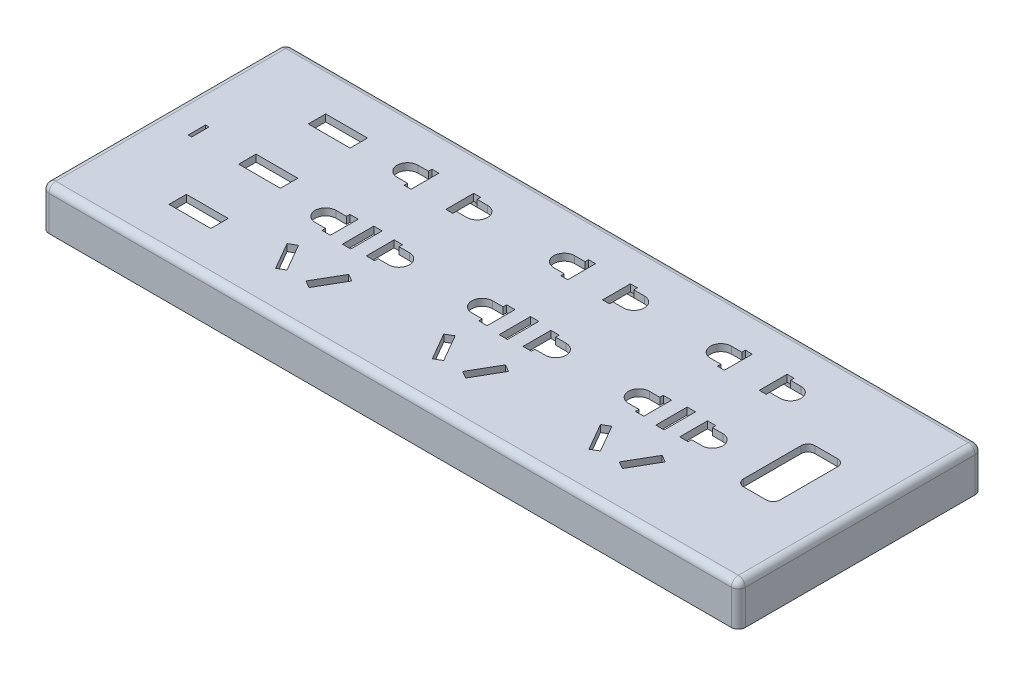
SolidWorks part; units mm, degrees
material "ABS"
ref_plane "前视基准面" through (0, 0, 0) normal (0, 0, 1) x (1, 0, 0)
ref_plane "上视基准面" through (0, 0, 0) normal (0, 1, 0) x (1, 0, 0)
ref_plane "右视基准面" through (0, 0, 0) normal (1, 0, 0) x (0, 0, -1)
ref_plane "BoxInnerTop" through (0, 0, 0) normal (0, 1, 0) x (1, 0, 0)
ref_plane "ConnectFace" through (0, -10, 0) normal (0, 1, 0) x (1, 0, 0)
sketch "SketchRec" plane through (0, 0, 0) normal (0, 1, 0) x (1, 0, 0)
  line L1 (-100, -35) -> (100, -35)
  line L2 (-100, -35) -> (-100, 35)
  line L3 (-100, 35) -> (100, 35)
  line L4 (100, -35) -> (100, 35)
  line L5 (-100, -35) -> (100, 35) construction
  line L6 (-100, 35) -> (100, -35) construction
  point P0 (0, 0)
  dimension "L" = 200
  dimension "KD" = 70
extrude "RectangleBox" add sketch "SketchRec" along normal blind 2 and the other way blind 10
fillet "RectangleR" radius 2 8 edges at (-100, -4, 35) (-100, -4, -35) (100, -4, -35) (100, -4, 35) (100, 2, 0) (0, 2, -35) (-100, 2, 0) (0, 2, 35)
shell "RectangleC" thickness 2 removed face at (0, -10, 0)
sketch "SketchCircle" [suppressed] plane through (0, 0, 0) normal (0, 1, 0) x (1, 0, 0)
  circle A0 centre (0, 0) radius 80
  dimension "D1" = 160
extrude "CircleBox" [suppressed] add sketch "SketchCircle" along normal blind 2 and the other way blind 10 contours A0
fillet "CircleR" [suppressed] radius 2
shell "CircleC" [suppressed] thickness 2
sketch "SButtonCut" plane through (0, -10, 0) normal (0, 1, 0) x (1, 0, 0)
  line L4 (83.25, 10.25) -> (76.75, 10.25)
  line L5 (85.25, -8.25) -> (85.25, 8.25)
  line L6 (76.75, -10.25) -> (83.25, -10.25)
  line L7 (74.75, 8.25) -> (74.75, -8.25)
  line L8 (83.25, 10.25) -> (76.75, 10.25)
  line L9 (85.25, -8.25) -> (85.25, 8.25)
  line L10 (76.75, -10.25) -> (83.25, -10.25)
  line L11 (74.75, 8.25) -> (74.75, -8.25)
  arc A4 (85.25, 8.25) -> (83.25, 10.25) centre (83.25, 8.25) ccw
  arc A5 (83.25, -10.25) -> (85.25, -8.25) centre (83.25, -8.25) ccw
  arc A6 (74.75, -8.25) -> (76.75, -10.25) centre (76.75, -8.25) ccw
  arc A7 (76.75, 10.25) -> (74.75, 8.25) centre (76.75, 8.25) ccw
  arc A8 (85.25, 8.25) -> (83.25, 10.25) centre (83.25, 8.25) ccw
  arc A9 (83.25, -10.25) -> (85.25, -8.25) centre (83.25, -8.25) ccw
  arc A10 (74.75, -8.25) -> (76.75, -10.25) centre (76.75, -8.25) ccw
  arc A11 (76.75, 10.25) -> (74.75, 8.25) centre (76.75, 8.25) ccw
  dimension "D1" = 0
extrude "FButtonCut" cut sketch "SButtonCut" along normal through all
sketch "SLEDCut" plane through (0, -10, 0) normal (0, 1, 0) x (1, 0, 0)
  line L4 (-90.5, -2.5) -> (-89.5, -2.5)
  line L5 (-89.5, -2.5) -> (-89.5, 2.5)
  line L6 (-89.5, 2.5) -> (-90.5, 2.5)
  line L7 (-90.5, 2.5) -> (-90.5, -2.5)
  line L8 (-90.5, -2.5) -> (-89.5, -2.5)
  line L9 (-89.5, -2.5) -> (-89.5, 2.5)
  line L10 (-89.5, 2.5) -> (-90.5, 2.5)
  line L11 (-90.5, 2.5) -> (-90.5, -2.5)
  dimension "D1" = 0
extrude "FLEDCut" cut sketch "SLEDCut" along normal through all
sketch "SSlotA" plane through (0, -10, 0) normal (0, 1, 0) x (1, 0, 0)
  line L4 (-38.8, 1.5) -> (-41.2, 1.5)
  line L5 (-38.8, -7.5) -> (-38.8, 1.5)
  line L6 (-41.2, -7.5) -> (-38.8, -7.5)
  line L7 (-45.15, -7) -> (-45.15, 1)
  line L8 (-47.55, -7) -> (-45.15, -7)
  line L9 (-47.55, -6) -> (-47.55, -7)
  line L10 (-50.55, -6) -> (-47.55, -6)
  line L11 (-47.55, 0) -> (-50.55, 0)
  line L12 (-47.55, 1) -> (-47.55, 0)
  line L13 (-45.15, 1) -> (-47.55, 1)
  line L14 (-45.15, -7) -> (-45.15, 1)
  line L15 (-47.55, -7) -> (-45.15, -7)
  line L16 (-47.55, -6) -> (-47.55, -7)
  line L17 (-50.55, -6) -> (-47.55, -6)
  line L18 (-47.55, 0) -> (-50.55, 0)
  line L19 (-47.55, 1) -> (-47.55, 0)
  line L20 (-45.15, 1) -> (-47.55, 1)
  line L21 (-41.2, 1.5) -> (-41.2, -7.5)
  line L22 (-38.8, 1.5) -> (-41.2, 1.5)
  line L23 (-38.8, -7.5) -> (-38.8, 1.5)
  line L24 (-41.2, -7.5) -> (-38.8, -7.5)
  line L25 (-41.2, 1.5) -> (-41.2, -7.5)
  line L26 (-37.2831, -21.8942) -> (-35.2047, -23.0942)
  line L27 (-35.2047, -23.0942) -> (-30.7047, -15.3)
  line L28 (-30.7047, -15.3) -> (-32.7831, -14.1)
  line L29 (-32.45, 0) -> (-32.45, 1)
  line L30 (-29.45, 0) -> (-32.45, 0)
  line L31 (-32.45, -6) -> (-29.45, -6)
  line L32 (-32.45, -7) -> (-32.45, -6)
  line L33 (-34.85, -7) -> (-32.45, -7)
  line L34 (-34.85, 1) -> (-34.85, -7)
  line L35 (-32.45, 1) -> (-34.85, 1)
  line L36 (-32.45, 0) -> (-32.45, 1)
  line L37 (-29.45, 0) -> (-32.45, 0)
  line L38 (-32.45, -6) -> (-29.45, -6)
  line L39 (-32.45, -7) -> (-32.45, -6)
  line L40 (-34.85, -7) -> (-32.45, -7)
  line L41 (-34.85, 1) -> (-34.85, -7)
  line L42 (-32.45, 1) -> (-34.85, 1)
  line L43 (-32.7831, -14.1) -> (-37.2831, -21.8942)
  line L44 (-37.2831, -21.8942) -> (-35.2047, -23.0942)
  line L45 (-35.2047, -23.0942) -> (-30.7047, -15.3)
  line L46 (-30.7047, -15.3) -> (-32.7831, -14.1)
  line L47 (-32.7831, -14.1) -> (-37.2831, -21.8942)
  line L48 (-49.2953, -15.3) -> (-44.7953, -23.0942)
  line L49 (-47.2169, -14.1) -> (-49.2953, -15.3)
  line L50 (-42.7169, -21.8942) -> (-47.2169, -14.1)
  line L51 (-44.7953, -23.0942) -> (-42.7169, -21.8942)
  line L52 (-49.2953, -15.3) -> (-44.7953, -23.0942)
  line L53 (-47.2169, -14.1) -> (-49.2953, -15.3)
  line L54 (-42.7169, -21.8942) -> (-47.2169, -14.1)
  line L55 (-44.7953, -23.0942) -> (-42.7169, -21.8942)
  arc A1 (-50.55, 0) -> (-50.55, -6) centre (-50.55, -3) ccw
  arc A2 (-50.55, 0) -> (-50.55, -6) centre (-50.55, -3) ccw
  arc A3 (-29.45, -6) -> (-29.45, 0) centre (-29.45, -3) ccw
  arc A4 (-29.45, -6) -> (-29.45, 0) centre (-29.45, -3) ccw
  dimension "D1" = 0
  dimension "D2" = 0
  dimension "D3" = 0
  dimension "D4" = 0
  dimension "D5" = 0
extrude "FSlotACut" cut sketch "SSlotA" along normal through all
sketch "SSlotA2" plane through (0, -10, 0) normal (0, 1, 0) x (1, 0, 0)
  line L4 (6.2, 1.5) -> (3.8, 1.5)
  line L5 (6.2, -7.5) -> (6.2, 1.5)
  line L6 (3.8, -7.5) -> (6.2, -7.5)
  line L7 (-0.15, -7) -> (-0.15, 1)
  line L8 (-2.55, -7) -> (-0.15, -7)
  line L9 (-2.55, -6) -> (-2.55, -7)
  line L10 (-5.55, -6) -> (-2.55, -6)
  line L11 (-2.55, 0) -> (-5.55, 0)
  line L12 (-2.55, 1) -> (-2.55, 0)
  line L13 (-0.15, 1) -> (-2.55, 1)
  line L14 (-0.15, -7) -> (-0.15, 1)
  line L15 (-2.55, -7) -> (-0.15, -7)
  line L16 (-2.55, -6) -> (-2.55, -7)
  line L17 (-5.55, -6) -> (-2.55, -6)
  line L18 (-2.55, 0) -> (-5.55, 0)
  line L19 (-2.55, 1) -> (-2.55, 0)
  line L20 (-0.15, 1) -> (-2.55, 1)
  line L21 (3.8, 1.5) -> (3.8, -7.5)
  line L22 (6.2, 1.5) -> (3.8, 1.5)
  line L23 (6.2, -7.5) -> (6.2, 1.5)
  line L24 (3.8, -7.5) -> (6.2, -7.5)
  line L25 (3.8, 1.5) -> (3.8, -7.5)
  line L26 (7.7169, -21.8942) -> (9.7953, -23.0942)
  line L27 (9.7953, -23.0942) -> (14.2953, -15.3)
  line L28 (14.2953, -15.3) -> (12.2169, -14.1)
  line L29 (12.55, 0) -> (12.55, 1)
  line L30 (15.55, 0) -> (12.55, 0)
  line L31 (12.55, -6) -> (15.55, -6)
  line L32 (12.55, -7) -> (12.55, -6)
  line L33 (10.15, -7) -> (12.55, -7)
  line L34 (10.15, 1) -> (10.15, -7)
  line L35 (12.55, 1) -> (10.15, 1)
  line L36 (12.55, 0) -> (12.55, 1)
  line L37 (15.55, 0) -> (12.55, 0)
  line L38 (12.55, -6) -> (15.55, -6)
  line L39 (12.55, -7) -> (12.55, -6)
  line L40 (10.15, -7) -> (12.55, -7)
  line L41 (10.15, 1) -> (10.15, -7)
  line L42 (12.55, 1) -> (10.15, 1)
  line L43 (12.2169, -14.1) -> (7.7169, -21.8942)
  line L44 (7.7169, -21.8942) -> (9.7953, -23.0942)
  line L45 (9.7953, -23.0942) -> (14.2953, -15.3)
  line L46 (14.2953, -15.3) -> (12.2169, -14.1)
  line L47 (12.2169, -14.1) -> (7.7169, -21.8942)
  line L48 (-4.2953, -15.3) -> (0.2047, -23.0942)
  line L49 (-2.2169, -14.1) -> (-4.2953, -15.3)
  line L50 (2.2831, -21.8942) -> (-2.2169, -14.1)
  line L51 (0.2047, -23.0942) -> (2.2831, -21.8942)
  line L52 (-4.2953, -15.3) -> (0.2047, -23.0942)
  line L53 (-2.2169, -14.1) -> (-4.2953, -15.3)
  line L54 (2.2831, -21.8942) -> (-2.2169, -14.1)
  line L55 (0.2047, -23.0942) -> (2.2831, -21.8942)
  arc A1 (-5.55, 0) -> (-5.55, -6) centre (-5.55, -3) ccw
  arc A2 (-5.55, 0) -> (-5.55, -6) centre (-5.55, -3) ccw
  arc A3 (15.55, -6) -> (15.55, 0) centre (15.55, -3) ccw
  arc A4 (15.55, -6) -> (15.55, 0) centre (15.55, -3) ccw
  dimension "D1" = 0
  dimension "D2" = 0
  dimension "D3" = 0
  dimension "D4" = 0
  dimension "D5" = 0
extrude "FSlotA2Cut" cut sketch "SSlotA2" along normal through all
sketch "SSlotA3" plane through (0, -10, 0) normal (0, 1, 0) x (1, 0, 0)
  line L4 (51.2, 1.5) -> (48.8, 1.5)
  line L5 (51.2, -7.5) -> (51.2, 1.5)
  line L6 (48.8, -7.5) -> (51.2, -7.5)
  line L7 (44.85, -7) -> (44.85, 1)
  line L8 (42.45, -7) -> (44.85, -7)
  line L9 (42.45, -6) -> (42.45, -7)
  line L10 (39.45, -6) -> (42.45, -6)
  line L11 (42.45, 0) -> (39.45, 0)
  line L12 (42.45, 1) -> (42.45, 0)
  line L13 (44.85, 1) -> (42.45, 1)
  line L14 (44.85, -7) -> (44.85, 1)
  line L15 (42.45, -7) -> (44.85, -7)
  line L16 (42.45, -6) -> (42.45, -7)
  line L17 (39.45, -6) -> (42.45, -6)
  line L18 (42.45, 0) -> (39.45, 0)
  line L19 (42.45, 1) -> (42.45, 0)
  line L20 (44.85, 1) -> (42.45, 1)
  line L21 (48.8, 1.5) -> (48.8, -7.5)
  line L22 (51.2, 1.5) -> (48.8, 1.5)
  line L23 (51.2, -7.5) -> (51.2, 1.5)
  line L24 (48.8, -7.5) -> (51.2, -7.5)
  line L25 (48.8, 1.5) -> (48.8, -7.5)
  line L26 (52.7169, -21.8942) -> (54.7953, -23.0942)
  line L27 (54.7953, -23.0942) -> (59.2953, -15.3)
  line L28 (59.2953, -15.3) -> (57.2169, -14.1)
  line L29 (57.55, 0) -> (57.55, 1)
  line L30 (60.55, 0) -> (57.55, 0)
  line L31 (57.55, -6) -> (60.55, -6)
  line L32 (57.55, -7) -> (57.55, -6)
  line L33 (55.15, -7) -> (57.55, -7)
  line L34 (55.15, 1) -> (55.15, -7)
  line L35 (57.55, 1) -> (55.15, 1)
  line L36 (57.55, 0) -> (57.55, 1)
  line L37 (60.55, 0) -> (57.55, 0)
  line L38 (57.55, -6) -> (60.55, -6)
  line L39 (57.55, -7) -> (57.55, -6)
  line L40 (55.15, -7) -> (57.55, -7)
  line L41 (55.15, 1) -> (55.15, -7)
  line L42 (57.55, 1) -> (55.15, 1)
  line L43 (57.2169, -14.1) -> (52.7169, -21.8942)
  line L44 (52.7169, -21.8942) -> (54.7953, -23.0942)
  line L45 (54.7953, -23.0942) -> (59.2953, -15.3)
  line L46 (59.2953, -15.3) -> (57.2169, -14.1)
  line L47 (57.2169, -14.1) -> (52.7169, -21.8942)
  line L48 (40.7047, -15.3) -> (45.2047, -23.0942)
  line L49 (42.7831, -14.1) -> (40.7047, -15.3)
  line L50 (47.2831, -21.8942) -> (42.7831, -14.1)
  line L51 (45.2047, -23.0942) -> (47.2831, -21.8942)
  line L52 (40.7047, -15.3) -> (45.2047, -23.0942)
  line L53 (42.7831, -14.1) -> (40.7047, -15.3)
  line L54 (47.2831, -21.8942) -> (42.7831, -14.1)
  line L55 (45.2047, -23.0942) -> (47.2831, -21.8942)
  arc A1 (39.45, 0) -> (39.45, -6) centre (39.45, -3) ccw
  arc A2 (39.45, 0) -> (39.45, -6) centre (39.45, -3) ccw
  arc A3 (60.55, -6) -> (60.55, 0) centre (60.55, -3) ccw
  arc A4 (60.55, -6) -> (60.55, 0) centre (60.55, -3) ccw
  dimension "D1" = 0
  dimension "D2" = 0
  dimension "D3" = 0
  dimension "D4" = 0
  dimension "D5" = 0
extrude "FSlotA3Cut" cut sketch "SSlotA3" along normal through all
sketch "SSlotB" plane through (0, -10, 0) normal (0, 1, 0) x (1, 0, 0)
  line L7 (-45, 16) -> (-45, 24)
  line L8 (-47, 16) -> (-45, 16)
  line L9 (-47, 17) -> (-47, 16)
  line L10 (-50, 17) -> (-47, 17)
  line L11 (-47, 23) -> (-50, 23)
  line L12 (-47, 24) -> (-47, 23)
  line L13 (-45, 24) -> (-47, 24)
  line L14 (-45, 16) -> (-45, 24)
  line L15 (-47, 16) -> (-45, 16)
  line L16 (-47, 17) -> (-47, 16)
  line L17 (-50, 17) -> (-47, 17)
  line L18 (-47, 23) -> (-50, 23)
  line L19 (-47, 24) -> (-47, 23)
  line L20 (-45, 24) -> (-47, 24)
  line L21 (-33, 17) -> (-30, 17)
  line L22 (-30, 23) -> (-33, 23)
  line L23 (-33, 23) -> (-33, 24)
  line L24 (-33, 24) -> (-35, 24)
  line L25 (-35, 24) -> (-35, 16)
  line L26 (-35, 16) -> (-33, 16)
  line L27 (-33, 16) -> (-33, 17)
  line L28 (-33, 17) -> (-30, 17)
  line L29 (-30, 23) -> (-33, 23)
  line L30 (-33, 23) -> (-33, 24)
  line L31 (-33, 24) -> (-35, 24)
  line L32 (-35, 24) -> (-35, 16)
  line L33 (-35, 16) -> (-33, 16)
  line L34 (-33, 16) -> (-33, 17)
  arc A1 (-50, 23) -> (-50, 17) centre (-50, 20) ccw
  arc A2 (-50, 23) -> (-50, 17) centre (-50, 20) ccw
  arc A3 (-30, 17) -> (-30, 23) centre (-30, 20) ccw
  arc A4 (-30, 17) -> (-30, 23) centre (-30, 20) ccw
  dimension "D1" = 0
  dimension "D2" = 0
extrude "FSlotBCut" cut sketch "SSlotB" along normal through all
sketch "SSlotB2" plane through (0, -10, 0) normal (0, 1, 0) x (1, 0, 0)
  line L7 (0, 16) -> (0, 24)
  line L8 (-2, 16) -> (0, 16)
  line L9 (-2, 17) -> (-2, 16)
  line L10 (-5, 17) -> (-2, 17)
  line L11 (-2, 23) -> (-5, 23)
  line L12 (-2, 24) -> (-2, 23)
  line L13 (0, 24) -> (-2, 24)
  line L14 (0, 16) -> (0, 24)
  line L15 (-2, 16) -> (0, 16)
  line L16 (-2, 17) -> (-2, 16)
  line L17 (-5, 17) -> (-2, 17)
  line L18 (-2, 23) -> (-5, 23)
  line L19 (-2, 24) -> (-2, 23)
  line L20 (0, 24) -> (-2, 24)
  line L21 (12, 17) -> (15, 17)
  line L22 (15, 23) -> (12, 23)
  line L23 (12, 23) -> (12, 24)
  line L24 (12, 24) -> (10, 24)
  line L25 (10, 24) -> (10, 16)
  line L26 (10, 16) -> (12, 16)
  line L27 (12, 16) -> (12, 17)
  line L28 (12, 17) -> (15, 17)
  line L29 (15, 23) -> (12, 23)
  line L30 (12, 23) -> (12, 24)
  line L31 (12, 24) -> (10, 24)
  line L32 (10, 24) -> (10, 16)
  line L33 (10, 16) -> (12, 16)
  line L34 (12, 16) -> (12, 17)
  arc A1 (-5, 23) -> (-5, 17) centre (-5, 20) ccw
  arc A2 (-5, 23) -> (-5, 17) centre (-5, 20) ccw
  arc A3 (15, 17) -> (15, 23) centre (15, 20) ccw
  arc A4 (15, 17) -> (15, 23) centre (15, 20) ccw
  dimension "D1" = 0
  dimension "D2" = 0
extrude "FSlotB2Cut" cut sketch "SSlotB2" along normal through all
sketch "SSlotB3" plane through (0, -10, 0) normal (0, 1, 0) x (1, 0, 0)
  line L7 (45, 16) -> (45, 24)
  line L8 (43, 16) -> (45, 16)
  line L9 (43, 17) -> (43, 16)
  line L10 (40, 17) -> (43, 17)
  line L11 (43, 23) -> (40, 23)
  line L12 (43, 24) -> (43, 23)
  line L13 (45, 24) -> (43, 24)
  line L14 (45, 16) -> (45, 24)
  line L15 (43, 16) -> (45, 16)
  line L16 (43, 17) -> (43, 16)
  line L17 (40, 17) -> (43, 17)
  line L18 (43, 23) -> (40, 23)
  line L19 (43, 24) -> (43, 23)
  line L20 (45, 24) -> (43, 24)
  line L21 (57, 17) -> (60, 17)
  line L22 (60, 23) -> (57, 23)
  line L23 (57, 23) -> (57, 24)
  line L24 (57, 24) -> (55, 24)
  line L25 (55, 24) -> (55, 16)
  line L26 (55, 16) -> (57, 16)
  line L27 (57, 16) -> (57, 17)
  line L28 (57, 17) -> (60, 17)
  line L29 (60, 23) -> (57, 23)
  line L30 (57, 23) -> (57, 24)
  line L31 (57, 24) -> (55, 24)
  line L32 (55, 24) -> (55, 16)
  line L33 (55, 16) -> (57, 16)
  line L34 (57, 16) -> (57, 17)
  arc A1 (40, 23) -> (40, 17) centre (40, 20) ccw
  arc A2 (40, 23) -> (40, 17) centre (40, 20) ccw
  arc A3 (60, 17) -> (60, 23) centre (60, 20) ccw
  arc A4 (60, 17) -> (60, 23) centre (60, 20) ccw
  dimension "D1" = 0
  dimension "D2" = 0
extrude "FSlotB3Cut" cut sketch "SSlotB3" along normal through all
sketch "SSlotC" plane through (0, -10, 0) normal (0, 1, 0) x (1, 0, 0)
  line L4 (-64, 17.5) -> (-64, 22.5)
  line L5 (-64, 22.5) -> (-76, 22.5)
  line L6 (-76, 22.5) -> (-76, 17.5)
  line L7 (-76, 17.5) -> (-64, 17.5)
  line L8 (-64, 17.5) -> (-64, 22.5)
  line L9 (-64, 22.5) -> (-76, 22.5)
  line L10 (-76, 22.5) -> (-76, 17.5)
  line L11 (-76, 17.5) -> (-64, 17.5)
  dimension "D1" = 0
extrude "FSlotCCut" cut sketch "SSlotC" along normal through all
sketch "SSlotC2" plane through (0, -10, 0) normal (0, 1, 0) x (1, 0, 0)
  line L4 (-64, -2.5) -> (-64, 2.5)
  line L5 (-64, 2.5) -> (-76, 2.5)
  line L6 (-76, 2.5) -> (-76, -2.5)
  line L7 (-76, -2.5) -> (-64, -2.5)
  line L8 (-64, -2.5) -> (-64, 2.5)
  line L9 (-64, 2.5) -> (-76, 2.5)
  line L10 (-76, 2.5) -> (-76, -2.5)
  line L11 (-76, -2.5) -> (-64, -2.5)
  dimension "D1" = 0
extrude "FSlotC2Cut" cut sketch "SSlotC2" along normal through all
sketch "SSlotC3" plane through (0, -10, 0) normal (0, 1, 0) x (1, 0, 0)
  line L4 (-64, -22.5) -> (-64, -17.5)
  line L5 (-64, -17.5) -> (-76, -17.5)
  line L6 (-76, -17.5) -> (-76, -22.5)
  line L7 (-76, -22.5) -> (-64, -22.5)
  line L8 (-64, -22.5) -> (-64, -17.5)
  line L9 (-64, -17.5) -> (-76, -17.5)
  line L10 (-76, -17.5) -> (-76, -22.5)
  line L11 (-76, -22.5) -> (-64, -22.5)
  dimension "D1" = 0
extrude "FSlotC3Cut" cut sketch "SSlotC3" along normal through all
equation "\"H\"= 10"
equation "\"Tn\"= 2"
equation "\"D1@RectangleBox\"=\"Tn\""
equation "\"D2@RectangleBox\"=\"H\""
equation "\"D1@CircleBox\"=\"Tn\""
equation "\"D2@CircleBox\"=\"H\""
equation "\"DisCt@ConnectFace\"=\"H\""
